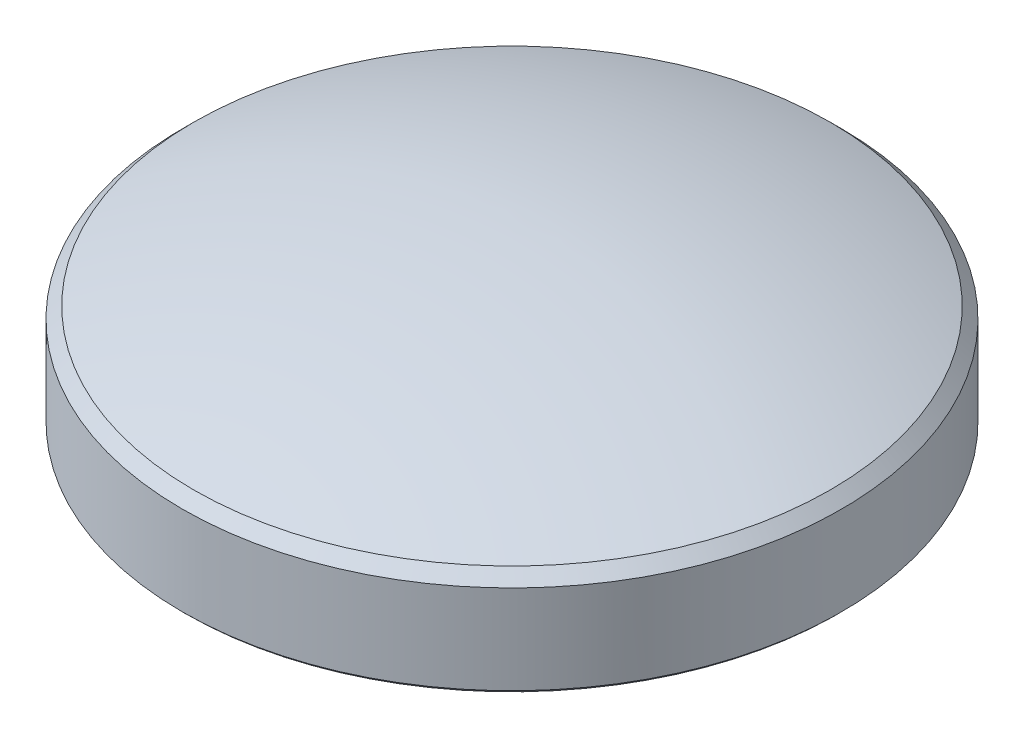
SolidWorks part; units mm, degrees
ref_plane "Front Plane" through (0, 0, 0) normal (0, 0, 1) x (1, 0, 0)
ref_plane "Top Plane" through (0, 0, 0) normal (0, 1, 0) x (1, 0, 0)
ref_plane "Right Plane" through (0, 0, 0) normal (1, 0, 0) x (0, 0, -1)
sketch "Sketch1" plane through (0, 0, 0) normal (0, 0, 1) x (1, 0, 0)
  line L0 (0, 18.15) -> (0, -13.9949) construction
  line L1 (0, 5.5562) -> (4.3656, 5.5562)
  line L2 (4.3656, 5.5562) -> (4.3656, 0)
  line L3 (15.24, -2.0637) -> (25.4, -2.0637)
  line L4 (25.4, -2.0637) -> (25.4, 5.5562)
  line L6 (0, 10.6363) -> (0, 5.5562)
  line L7 (4.3656, 0) -> (13.1763, 0)
  line L8 (0, 10.6363) -> (32.0025, 10.6363) construction
  line L11 (13.1763, 0) -> (15.24, -2.0637)
  arc A0 (0, 10.6363) -> (25.4, 5.5562) centre (0, -55.4037) cw
  point P12 (9.4456, 0)
  point P15 (20.1613, 0)
  point P22 (22.6979, 2.7781)
  dimension "D9" = 5.08
  dimension "D1" = 50.8
  dimension "D2" = 8.7312
  dimension "D3" = 5.08
  dimension "D4" = 5.5562
  dimension "D5" = 135
  dimension "D6" = 10.16
  dimension "D8" = 7.62
  dimension "D10" = 12.7
  dimension "D11" = 7.62
revolve "Revolve1" add sketch "Sketch1" angle 360 about L0
chamfer "Chamfer2" distance 0.254 angle 45 1 edges at (0, -2.0637, 25.4)
chamfer "Chamfer3" distance 0.508 angle 45 1 edges at (0, 5.5562, 25.4) first distance on face at (0, -1.8098, 25.4)
sketch "Sketch3" plane through (0, 0, 0) normal (0, 1, 0) x (1, 0, 0)
  line L0 (0, 18.923) -> (-17.78, -6.477)
  line L1 (-17.78, -6.477) -> (-5.9267, -0.127)
  line L2 (-5.9267, -0.127) -> (0, -6.477)
  line L3 (0, 19.6846) -> (0, -18.0216) construction
  line L4 (0, 18.923) -> (17.78, -6.477)
  line L5 (17.78, -6.477) -> (5.9267, -0.127)
  line L6 (5.9267, -0.127) -> (0, -6.477)
  circle A0 centre (0, 0) radius 18.923 construction
  dimension "D1" = 25.4
  dimension "D2" = 35.56
  dimension "D3" = 11.8533
  dimension "D4" = 6.35
curve "Curve1"
sketch "Sketch4" plane through (0, -2.0637, 0) normal (0, -1, 0) x (1, 0, 0)
  line L0 (0, 0) -> (19.05, 0) construction
  line L1 (0, 0) -> (-9.525, 16.4978) construction
  circle A0 centre (0, 0) radius 19.05 construction
  circle A1 centre (19.05, 0) radius 1.8986
  circle A2 centre (-9.525, 16.4978) radius 1.8987
  circle A3 centre (-9.525, -16.4978) radius 1.8987
  point P9 (17.3312, 0)
  dimension "D1" = 120
  dimension "D2" = 3.7973
  dimension "D3" = 38.1
extrude "Cut-Extrude1" cut sketch "Sketch4" against normal blind 5.08
equation "\"D2@Sketch3\"=1.4*\"D1@Sketch3\""
equation "\"D3@Sketch3\"=\"D2@Sketch3\"/3"
equation "\"D4@Sketch3\"=0.25*\"D1@Sketch3\""
